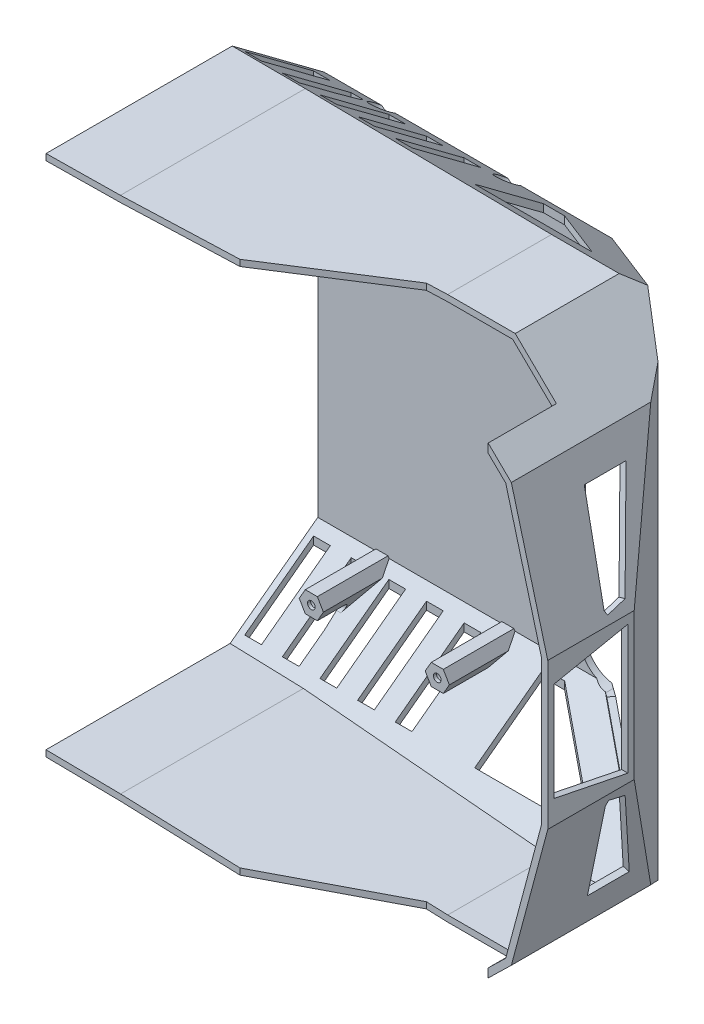
SolidWorks part; units mm, degrees
ref_plane "Alzado" through (0, 0, 0) normal (0, 0, 1) x (1, 0, 0)
ref_plane "Planta" through (0, 0, 0) normal (0, 1, 0) x (1, 0, 0)
ref_plane "Vista lateral" through (0, 0, 0) normal (1, 0, 0) x (0, 0, -1)
sketch "Croquis2" plane through (0, 0, 0) normal (0, 1, 0) x (1, 0, 0)
  line L1 (-132.5, 79) -> (132.5, 79)
  line L2 (-132.5, 79) -> (-132.5, -79)
  line L3 (-132.5, -79) -> (132.5, -79)
  line L4 (132.5, 79) -> (132.5, -79)
  line L5 (-132.5, 79) -> (132.5, -79) construction
  line L6 (-132.5, -79) -> (132.5, 79) construction
  point P0 (0, 0)
  dimension "D1" = 265
  dimension "D2" = 158
extrude "Saliente-Extruir1" add sketch "Croquis2" along normal blind 260
sketch "Croquis3" plane through (0, 260, 0) normal (0, 1, 0) x (1, 0, 0)
  line L0 (-132.5, -79) -> (-132.5, -29)
  line L1 (-132.5, 79) -> (-132.5, -79) construction
  line L2 (132.5, -79) -> (132.5, 79) construction
  line L3 (132.5, -29) -> (132.5, -79)
  line L4 (132.5, -79) -> (-132.5, -79)
  line L10 (-132.5, -29) -> (132.5, -29)
  dimension "D1" = 50
extrude "Cortar-Extruir1" cut sketch "Croquis3" against normal blind 260
sketch "Croquis37" plane through (0, 0, 29) normal (0, 0, 1) x (1, 0, 0)
  line L1 (-132.5, 260) -> (132.5, 260)
  line L2 (-132.5, 260) -> (-132.5, 0)
  line L3 (-132.5, 0) -> (132.5, 0)
  line L4 (132.5, 260) -> (132.5, 0)
extrude "Saliente-Extruir3" add sketch "Croquis37" along normal blind 25
sketch "Croquis5" plane through (0, 260, 0) normal (0, 1, 0) x (1, 0, 0)
  line L2 (102.4988, 23.7269) -> (25.1963, 79)
  line L3 (132.5, 79) -> (-132.5, 79) construction
  line L4 (127.5, -12.65) -> (127.5, -54)
  line L5 (132.5, -54) -> (-132.5, -54) construction
  line L6 (127.5, -12.65) -> (59.336, -12.65) construction
  line L9 (25.1963, 79) -> (132.5, 79)
  line L13 (132.5, 79) -> (132.5, -54)
  line L15 (132.5, -54) -> (127.5, -54)
  line L16 (127.5, -12.65) -> (102.4988, 23.7269)
  line L18 (-132.5, 79) -> (-112.5, 79)
  line L19 (-132.5, 79) -> (-132.5, -54)
  line L20 (-132.5, -54) -> (-112.5, -54)
  line L21 (-112.5, 79) -> (-112.5, -54)
  line L22 (-132.5, 79) -> (-132.5, -54) construction
  dimension "D1" = 20
  dimension "D2" = 77.3025
  dimension "D5" = 41.35
  dimension "D6" = 145.5
  dimension "D7" = 44.14
  dimension "D9" = 5
extrude "Cortar-Extruir2" cut sketch "Croquis5" against normal blind 260
sketch "Croquis7" plane through (0, 0, -79) normal (0, 0, -1) x (-1, 0, 0)
  line L0 (148.6772, 130) -> (-49851.3228, 130) construction
  line L1 (-127.5, 165) -> (-110.0833, 230)
  line L2 (163.75, 130) -> (163.75, 255) construction
  line L3 (-110.0833, 230) -> (-78.1256, 261.138)
  line L5 (-127.5, 250.0463) -> (-127.5, 165)
  line L6 (-78.1256, 261.138) -> (76.9059, 255.4756)
  line L8 (76.9059, 255.4756) -> (112.5, 255)
  line L17 (112.5, 0) -> (112.5, 260) construction
  line L18 (163.75, 255) -> (112.5, 255) construction
  line L27 (-127.5, 266.138) -> (112.5, 266.138)
  line L28 (-127.5, 266.138) -> (-127.5, 250.0463)
  line L30 (112.5, 266.138) -> (112.5, 255)
  line L39 (-78.1256, -1.138) -> (76.9059, 4.5244)
  line L40 (-110.0833, 30) -> (-78.1256, -1.138)
  line L41 (-127.5, 95) -> (-110.0833, 30)
  line L42 (-127.5, 9.9537) -> (-127.5, 95)
  line L43 (-127.5, -6.138) -> (-127.5, 9.9537)
  line L44 (-127.5, -6.138) -> (112.5, -6.138)
  line L45 (112.5, -6.138) -> (112.5, 5)
  line L46 (76.9059, 4.5244) -> (112.5, 5)
  line L47 (-127.5, 0) -> (-127.5, 260) construction
  dimension "D1" = 130
  dimension "D2" = 35
  dimension "D3" = 100
  dimension "D4" = 15
  dimension "D5" = 125
  dimension "D6" = 44.6192
  dimension "D7" = 5
  dimension "D9" = 2.092
  dimension "D8" = 155.0315
  dimension "D11" = 35.5941
  dimension "D10" = 51.25
extrude "Cortar-Extruir20" cut sketch "Croquis7" against normal through all
sketch "Croquis8" plane through (-112.5, 0, -18.7219) normal (1, 0, 0) x (0, 0, -1)
  line L1 (60.2781, 263.609) -> (4.7914, 263.609)
  line L4 (-99.1508, 130) -> (49900.8492, 130) construction
  line L6 (4.7914, 263.609) -> (60.2781, 222.2255)
  line L7 (60.2781, 5) -> (60.2781, 255) construction
  line L13 (60.2781, 263.609) -> (60.2781, 222.2255)
  line L14 (60.2781, -3.609) -> (60.2781, 37.7745)
  line L15 (4.7914, -3.609) -> (60.2781, 37.7745)
  line L16 (60.2781, -3.609) -> (4.7914, -3.609)
  dimension "D3" = 130
  dimension "D4" = 92.2255
  dimension "D1" = 55.4867
  dimension "D2" = 69.2197
extrude "Cortar-Extruir4" cut sketch "Croquis8" along normal up to surface (240 mm away) up to face at (127.5, 130, 33.325)
shell "Vaciado1" thickness 3 removed face at (29.0731, 130, 54) removed face at (-112.5, 130, -20.0187)
sketch "Croquis9" plane through (45.9013, 0, -64.1955) normal (0.5816, 0, -0.8134) x (-0.8134, 0, -0.5816)
  line L4 (-47.8731, 250.7643) -> (-66.5772, 235.9397)
  line L8 (22.4532, 39.7433) -> (22.4532, 220.2567)
  line L9 (22.4532, 220.2567) -> (-47.8731, 250.7643)
  line L12 (22.4532, 39.7433) -> (22.4532, 220.2567)
  line L24 (-47.8731, 250.7643) -> (-66.5772, 235.9397)
  line L25 (-66.5772, 24.0603) -> (-47.8731, 9.2357)
  line L26 (-66.5772, 24.0603) -> (-47.8731, 9.2357)
  line L27 (-66.5772, 235.9397) -> (-66.5772, 24.0603)
  line L28 (-66.5772, 235.9397) -> (-66.5772, 24.0603)
  line L32 (22.4532, 220.2567) -> (-47.8731, 250.7643)
  line L36 (-47.8731, 9.2357) -> (22.4532, 39.7433)
  line L37 (-47.8731, 9.2357) -> (22.4532, 39.7433)
  dimension "D1" = 3
extrude "Cortar-Extruir5" cut sketch "Croquis9" against normal up to next
sketch "Croquis41" plane through (0, 0, -76) normal (0, 0, 1) x (1, 0, 0)
  line L5 (127.5, 130) -> (-31.812, 130) construction
  line L6 (127.5, 95) -> (127.5, 165) construction
  line L11 (25.1963, 222.2255) -> (-112.5, 222.2255) construction
  line L12 (12.5137, 222.2255) -> (60.2602, 222.2255)
  line L13 (12.5137, 222.2255) -> (12.5137, 37.7745)
  line L14 (12.5137, 37.7745) -> (60.2602, 37.7745)
  line L15 (60.2602, 222.2255) -> (60.2602, 37.7745)
  point P6 (60.2602, 130)
  dimension "D1" = 67.2398
  dimension "D2" = 47.7465
extrude "Cortar-Extruir22" cut sketch "Croquis41" along normal blind 10 from surface starting at face at (-43.6518, 130, -79)
sketch "Croquis43" plane through (127.5, 0, 0) normal (1, 0, 0) x (0, 0, -1)
  line L0 (-54, 130) -> (79, 130) construction
  line L1 (-54, 95) -> (-54, 165) construction
  line L2 (79, 222.2255) -> (79, 37.7745) construction
fillet "Redondeo1" radius 15 2 edges at (12.5137, 37.7745, -76.491) (12.5137, 222.2255, -76.491)
sketch "Croquis18" plane through (127.5, 0, -6.591) normal (1, 0, 0) x (0, 0, -1)
  line L0 (-60.591, 130) -> (-19.241, 130) construction
  line L1 (-60.591, 95) -> (-60.591, 165) construction
  line L2 (-19.241, 95) -> (-19.241, 165) construction
  line L13 (-22.241, 99.1344) -> (-22.241, 160.8656)
  line L49 (-22.241, 160.8656) -> (-57.591, 153.6853)
  line L50 (-57.591, 153.6853) -> (-57.591, 106.3147)
  line L53 (-57.591, 106.3147) -> (-22.241, 99.1344)
  point P8 (-22.241, 130)
  point P9 (-57.591, 130)
  dimension "D1" = 3
  dimension "D2" = 3
  dimension "D3" = 36.0719
  dimension "D4" = 61.7313
extrude "Cortar-Extruir13" cut sketch "Croquis18" against normal up to next
sketch "Croquis19" plane through (160.2091, 42.9279, 0) normal (0.9659, 0.2588, 0) x (0, 0, -1)
  line L5 (-23.0184, 178.6713) -> (-3.0184, 178.6713)
  line L6 (-3.0184, 178.6713) -> (-15.5301, 132.1742)
  line L7 (-15.5301, 132.1742) -> (-24.4349, 130.0111)
  line L8 (-24.4349, 130.0111) -> (-25.5496, 132.1742)
  line L9 (-25.5496, 132.1742) -> (-23.0184, 178.6713)
  line L10 (-54, 126.3783) -> (-12.65, 126.3783) construction
  line L12 (-54, 193.6713) -> (12.6915, 193.6713) construction
  line L13 (12.6915, 193.6713) -> (-12.65, 126.3783) construction
  dimension "D1" = 20
  dimension "D2" = 48.151
  dimension "D3" = 46.497
  dimension "D4" = 8.9049
  dimension "D5" = 2.4334
  dimension "D6" = 149.621
  dimension "D7" = 15
  dimension "D8" = 3.6328
  dimension "D9" = 4.7379
extrude "Cortar-Extruir14" cut sketch "Croquis19" against normal up to next
sketch "Croquis40" plane through (95.2091, -25.5112, 0) normal (0.9659, -0.2588, 0) x (0, 0, -1)
  line L0 (-21.4902, 72.4694) -> (-1.4902, 72.4694)
  line L1 (-1.4902, 72.4694) -> (-15.3836, 118.5715)
  line L2 (-15.3836, 118.5715) -> (-23.9014, 121.1516)
  line L3 (-23.9014, 121.1516) -> (-24.9704, 118.9694)
  line L4 (-24.9704, 118.9694) -> (-21.4902, 72.4694)
  line L5 (-54, 57.4694) -> (12.6915, 57.4694) construction
  line L6 (-54, 124.7624) -> (-12.65, 124.7624) construction
  line L7 (-12.65, 124.7624) -> (12.6915, 57.4694) construction
  dimension "D1" = 20
  dimension "D2" = 15
  dimension "D3" = 48.15
  dimension "D4" = 8.9
  dimension "D5" = 2.43
  dimension "D6" = 46.5
  dimension "D7" = 123.623
  dimension "D8" = 149.62
  dimension "D9" = 3.6107
  dimension "D10" = 4.74
extrude "Cortar-Extruir21" cut sketch "Croquis40" against normal through all
sketch "Croquis51" plane through (0, 0, 0) normal (0, 1, 0) x (1, 0, 0)
  line L0 (-96.5, 54.5281) -> (-96.5, 79) construction
  line L2 (-101.5, 71) -> (-101.5, 38.0562)
  line L3 (-101.5, 38.0562) -> (-109.5, 38.0562)
  line L4 (-109.5, 71) -> (-109.5, 38.0562)
  line L5 (-105.5, 71) -> (-105.5, 38.0562) construction
  line L6 (-87.5, 71) -> (-87.5, 38.0562) construction
  line L7 (-112.5, 35.0562) -> (-76.3814, 35.0562) construction
  line L8 (-112.5, 79) -> (-112.5, 35.0562) construction
  line L9 (-101.5, 71) -> (-109.5, 71)
  line L10 (25.1963, 79) -> (-112.5, 79) construction
  line L11 (-101.5, 54.5281) -> (-91.5, 54.5281) construction
  line L12 (-91.5, 71) -> (-83.5, 71)
  line L13 (-83.5, 71) -> (-83.5, 38.0562)
  line L14 (-91.5, 38.0562) -> (-83.5, 38.0562)
  line L15 (-91.5, 71) -> (-91.5, 38.0562)
  line L16 (-78.5, 54.5281) -> (-78.5, 79) construction
  line L17 (-55.5, 54.5281) -> (-65.5, 54.5281) construction
  line L18 (-69.5, 71) -> (-69.5, 38.0562) construction
  line L19 (-51.5, 71) -> (-51.5, 38.0562) construction
  line L20 (-60.5, 54.5281) -> (-60.5, 79) construction
  line L21 (-65.5, 71) -> (-65.5, 38.0562)
  line L22 (-65.5, 38.0562) -> (-73.5, 38.0562)
  line L23 (-73.5, 71) -> (-73.5, 38.0562)
  line L24 (-65.5, 71) -> (-73.5, 71)
  line L25 (-55.5, 71) -> (-47.5, 71)
  line L26 (-47.5, 71) -> (-47.5, 38.0562)
  line L27 (-55.5, 38.0562) -> (-47.5, 38.0562)
  line L28 (-55.5, 71) -> (-55.5, 38.0562)
  line L29 (-42.5, 54.5281) -> (-42.5, 79) construction
  line L30 (-29.5, 71) -> (-29.5, 38.0562)
  line L31 (-29.5, 38.0562) -> (-37.5, 38.0562)
  line L32 (-37.5, 71) -> (-37.5, 38.0562)
  line L33 (-29.5, 71) -> (-37.5, 71)
  line L34 (0.5, 71) -> (10.5954, 71)
  line L35 (10.5954, 71) -> (56.6692, 38.0562)
  line L36 (56.6692, 38.0562) -> (0.5, 38.0562)
  line L37 (0.5, 38.0562) -> (0.5, 71)
  line L39 (85.2136, 36.0862) -> (25.1963, 79) construction
  dimension "D1" = 8
  dimension "D2" = 3
  dimension "D3" = 3
  dimension "D4" = 8
  dimension "D5" = 5
  dimension "D6" = 30
  dimension "D7" = 15
extrude "Cortar-Extruir28" cut sketch "Croquis51" along normal through all
sketch "Croquis52" plane through (0, 257, 0) normal (0, -1, 0) x (1, 0, 0)
  line L0 (98.9933, 54) -> (98.9933, 21.3497)
  line L1 (98.9933, 21.3497) -> (36.7794, 21.3497)
  line L2 (36.7794, 21.3497) -> (-19.7388, 54)
  line L3 (-76.9059, 54) -> (46.9674, 54) construction
  line L4 (-19.7388, 54) -> (98.9933, 54)
  line L6 (-76.9059, 54) -> (46.9674, 54) construction
  line L8 (110.0833, 54) -> (110.0833, -12.6915) construction
  dimension "D1" = 62.2139
  dimension "D2" = 11.09
  dimension "D3" = 118.7321
  dimension "D4" = 65.2714
extrude "Cortar-Extruir29" cut sketch "Croquis52" against normal through all and the other way through all
sketch "Croquis44" plane through (0, 0, -79) normal (0, 0, -1) x (-1, 0, 0)
  line L0 (76.9059, 4.5244) -> (112.5, 5) construction
  line L1 (112.5, 37.7745) -> (112.5, 5) construction
  line L2 (-46.9674, 0) -> (76.9059, 4.5244) construction
  line L3 (-127.5, 130) -> (112.5, 130) construction
  line L4 (-127.5, 95) -> (-127.5, 165) construction
  line L5 (112.5, 37.7745) -> (112.5, 222.2255) construction
  line L7 (87.5719, 35.1265) -> (84.6844, 40.1278)
  line L8 (84.6844, 40.1278) -> (78.9094, 40.1278)
  line L9 (78.9094, 40.1278) -> (76.0219, 35.1265)
  line L10 (76.0219, 35.1265) -> (78.9094, 30.1252)
  line L11 (78.9094, 30.1252) -> (84.6844, 30.1252)
  line L12 (84.6844, 30.1252) -> (87.5719, 35.1265)
  line L13 (27.3275, 35.1265) -> (24.44, 40.1278)
  line L14 (24.44, 40.1278) -> (18.665, 40.1278)
  line L15 (18.665, 40.1278) -> (15.7775, 35.1265)
  line L16 (15.7775, 35.1265) -> (18.665, 30.1252)
  line L17 (18.665, 30.1252) -> (24.44, 30.1252)
  line L18 (24.44, 30.1252) -> (27.3275, 35.1265)
  line L30 (24.44, 229.8748) -> (27.3275, 224.8735)
  line L31 (18.665, 229.8748) -> (24.44, 229.8748)
  line L32 (15.7775, 224.8735) -> (18.665, 229.8748)
  line L33 (18.665, 219.8722) -> (15.7775, 224.8735)
  line L34 (24.44, 219.8722) -> (18.665, 219.8722)
  line L35 (27.3275, 224.8735) -> (24.44, 219.8722)
  line L36 (84.6844, 229.8748) -> (87.5719, 224.8735)
  line L37 (78.9094, 229.8748) -> (84.6844, 229.8748)
  line L38 (76.0219, 224.8735) -> (78.9094, 229.8748)
  line L39 (78.9094, 219.8722) -> (76.0219, 224.8735)
  line L40 (84.6844, 219.8722) -> (78.9094, 219.8722)
  line L41 (87.5719, 224.8735) -> (84.6844, 219.8722)
  circle A0 centre (81.7969, 35.1265) radius 1.825 construction
  circle A1 centre (21.5525, 35.1265) radius 1.825 construction
  circle A4 centre (81.7969, 35.1265) radius 5.0013 construction
  circle A5 centre (21.5525, 35.1265) radius 5.0013 construction
  circle A10 centre (21.5525, 35.1265) radius 1.825
  circle A11 centre (81.7969, 35.1265) radius 1.825
  circle A12 centre (21.5525, 224.8735) radius 5.0013 construction
  circle A13 centre (81.7969, 224.8735) radius 5.0013 construction
  circle A14 centre (21.5525, 224.8735) radius 1.825 construction
  circle A15 centre (81.7969, 224.8735) radius 1.825 construction
  circle A16 centre (81.7969, 224.8735) radius 1.825
  circle A17 centre (21.5525, 224.8735) radius 1.825
  dimension "D1" = 3.65
  dimension "D2" = 3.65
  dimension "D9" = 3.65
  dimension "D10" = 3.65
  dimension "D3" = 30.534
  dimension "D4" = 30.7031
  dimension "D5" = 32.6021
  dimension "D6" = 60.2444
  dimension "D7" = 11.55
  dimension "D8" = 11.55
extrude "Saliente-Extruir4" add sketch "Croquis44" against normal blind 36.8 from surface starting at face at (-13.0829, 130, -79)
sketch "Croquis47" plane through (0, 0, -79) normal (0, 0, -1) x (-1, 0, 0)
  line L0 (86.043, 222.2255) -> (87.5719, 224.8735) construction
  line L1 (84.6844, 229.8748) -> (78.9094, 229.8748) construction
  line L2 (81.7969, 224.8455) -> (21.5525, 224.8455) construction
  line L3 (21.5525, 224.8455) -> (21.5525, 35.1265) construction
  line L4 (-12.5137, 207.2255) -> (-12.5137, 52.7745) construction
  line L5 (51.6747, 224.8455) -> (51.6747, 145.6844) construction
  line L6 (112.5, 130) -> (-12.5137, 130) construction
  line L7 (112.5, 37.7745) -> (112.5, 222.2255) construction
  line L8 (81.7969, 35.1545) -> (21.5525, 35.1545) construction
  circle A0 centre (81.7969, 224.8455) radius 1.825
  circle A1 centre (21.5525, 224.8455) radius 1.825
  circle A2 centre (21.5525, 35.1545) radius 1.825
  circle A3 centre (81.7969, 35.1545) radius 1.825
  dimension "D1" = 3.65
  dimension "D2" = 4.9873
  dimension "D3" = 5.0294
  dimension "D4" = 189.719
  dimension "D5" = 34.0662
extrude "Cortar-Extruir25" cut sketch "Croquis47" against normal through all
sketch "Croquis49" plane through (0, 0, -79) normal (0, 0, -1) x (-1, 0, 0)
  line L0 (84.6844, 229.8748) -> (78.9094, 229.8748) construction
  line L1 (81.7969, 224.8455) -> (21.5525, 224.8455) construction
  line L2 (21.5525, 224.8455) -> (21.5525, 35.1265) construction
  line L3 (-12.5137, 207.2255) -> (-12.5137, 52.7745) construction
  line L4 (51.6747, 224.8455) -> (51.6747, 134.2407) construction
  line L5 (112.5, 130) -> (-12.5137, 130) construction
  line L6 (112.5, 37.7745) -> (112.5, 222.2255) construction
  circle A0 centre (81.7969, 224.8455) radius 4
  circle A1 centre (21.5525, 224.8455) radius 4
  circle A2 centre (81.7969, 35.1545) radius 4
  circle A3 centre (21.5525, 35.1545) radius 4
  dimension "D1" = 8
  dimension "D2" = 5.775
  dimension "D3" = 5.0294
  dimension "D4" = 34.0662
extrude "Cortar-Extruir27" cut sketch "Croquis49" against normal offset from surface (35.3 mm away) 1.5 up to face at (-81.7969, 35.1265, -42.2)
sketch "Croquis48" plane through (-112.5, 0, 0) normal (-1, 0, 0) x (0, 0, 1)
  line L0 (-79, 37.7745) -> (-79, 30.1252)
  line L1 (-79, 30.1252) -> (-79, 35.1265) construction
  line L2 (-79, 30.1252) -> (-68.7438, 30.1252)
  line L3 (-68.7438, 30.1252) -> (-79, 37.7745)
  line L4 (-79, 222.2255) -> (-79, 229.8748)
  line L5 (-79, 229.8748) -> (-68.7438, 229.8748)
  line L6 (-68.7438, 229.8748) -> (-79, 222.2255)
extrude "Cortar-Extruir26" cut sketch "Croquis48" against normal through all
fillet "Redondeo2" radius 3 2 edges at (-81.2047, 229.8748, -63.7259) (-81.2047, 30.1252, -63.7259)
chamfer "Chaflán1" distance 10 angle 6.5 2 edges at (-83.5, 229.8748, -61.7147) (-83.5, 30.1252, -61.7147) first distance on face at (-83.5, 239.2329, -51.5943) first distance on face at (-83.5, 20.7671, -51.5943)
sketch "Croquis50" plane through (0, 0, 0) normal (0, 1, 0) x (1, 0, 0)
  line L1 (-102.9424, 71.869) -> (-90.1437, 71.869)
  line L2 (-102.9424, 71.869) -> (-102.9424, 42.7314)
  line L3 (-102.9424, 42.7314) -> (-90.1437, 42.7314)
  line L4 (-90.1437, 71.869) -> (-90.1437, 42.7314)
sketch "Croquis45" plane through (0, 0, -42.2) normal (0, 0, 1) x (1, 0, 0)
  circle A0 centre (-21.5525, 35.1265) radius 1.825
  dimension "D1" = 3.65
sketch "Croquis46" plane through (-112.5, 0, 0) normal (-1, 0, 0) x (0, 0, 1)
  line L0 (-79, 37.7745) -> (-79, 30.1252)
  line L1 (-79, 222.2255) -> (-79, 229.8748)
  line L2 (-79, 229.8748) -> (-68.7438, 229.8748)
  line L3 (-68.7438, 229.8748) -> (-79, 222.2255)
  line L4 (-79, 30.1252) -> (-68.7438, 30.1252)
  line L5 (-68.7438, 30.1252) -> (-79, 37.7745)
equation "\"A\"= 53'Largo"
equation "\"B\"= 26'Alto"
equation "\"C\"= 60'Ancho"
equation "\"D1@Croquis2\"=212+\"A\""
equation "\"D2@Croquis2\"=132+\"B\""
equation "\"D1@Saliente-Extruir1\"=200+\"C\""
equation "\"D1@Croquis7\"=(200+\"C\")/2"
equation "\"D3@Croquis8\"=(200+\"C\")/2"
